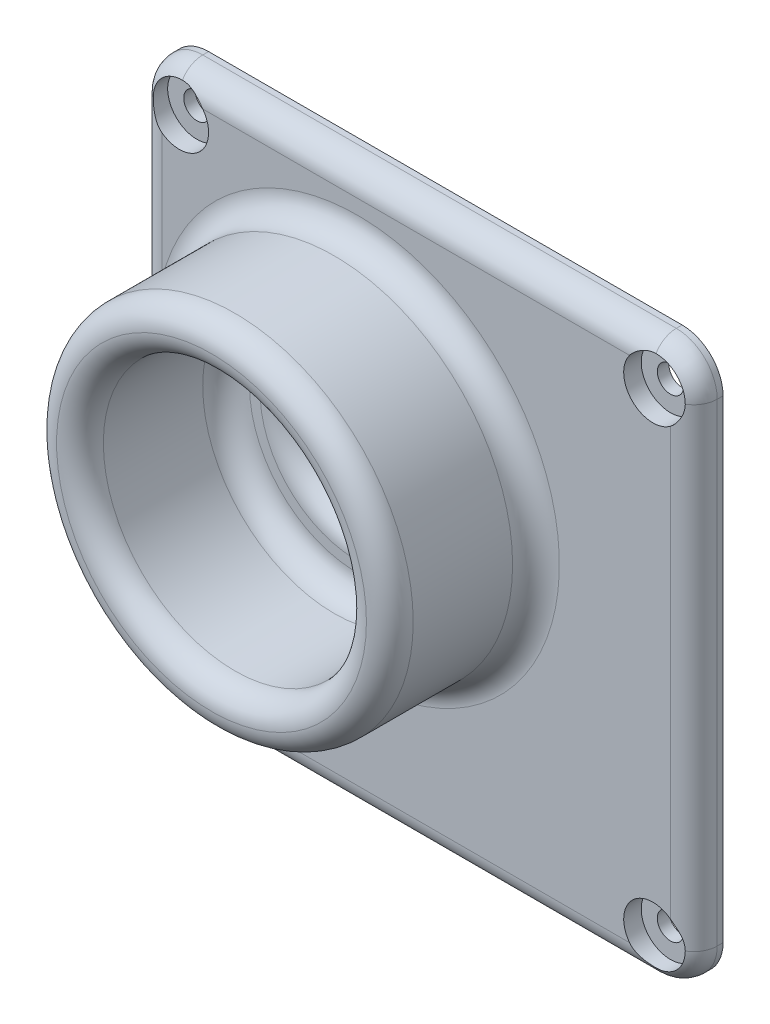
SolidWorks part; units mm, degrees
ref_plane "Front Plane" through (0, 0, 0) normal (1, 0, 0) x (0, 1, 0)
ref_plane "Top Plane" through (0, 0, 0) normal (0, 0, 1) x (0, 1, 0)
ref_plane "Right Plane" through (0, 0, 0) normal (0, 1, 0) x (-1, 0, 0)
sketch "Sketch1" plane through (0, 0, 0) normal (0, 0, 1) x (0, -1, 0)
  line L1 (-37.5, 37.5) -> (37.5, 37.5)
  line L2 (-37.5, 37.5) -> (-37.5, -37.5)
  line L3 (-37.5, -37.5) -> (37.5, -37.5)
  line L4 (37.5, 37.5) -> (37.5, -37.5)
  line L11 (-40.5, 40.5) -> (40.5, 40.5) construction
  line L12 (-40.5, 40.5) -> (-40.5, -40.5) construction
  line L13 (-40.5, -40.5) -> (40.5, -40.5) construction
  line L14 (40.5, 40.5) -> (40.5, -40.5) construction
  line L15 (-40.5, 40.5) -> (40.5, -40.5) construction
  line L16 (-40.5, -40.5) -> (40.5, 40.5) construction
  circle A0 centre (-40.5, 40.5) radius 2.25
  circle A1 centre (40.5, 40.5) radius 2.25
  circle A2 centre (40.5, -40.5) radius 2.25
  circle A3 centre (-40.5, -40.5) radius 2.25
  point P12 (0, 0)
  point P18 (-40.5, 0)
  point P19 (0, 40.5)
  point P20 (0, 37.5)
  point P21 (-37.5, 0)
  dimension "D8" = 4.5
  dimension "D9" = 4.5
  dimension "D3" = 75
  dimension "D4" = 75
  dimension "D7" = 3
sketch "Sketch2" plane through (0, 0, 0) normal (0, 0, 1) x (0, 1, 0)
  line L1 (47.5, -47.5) -> (-47.5, -47.5)
  line L2 (47.5, -47.5) -> (47.5, 47.5)
  line L3 (47.5, 47.5) -> (-47.5, 47.5)
  line L4 (-47.5, -47.5) -> (-47.5, 47.5)
  line L5 (47.5, -47.5) -> (-47.5, 47.5) construction
  line L6 (47.5, 47.5) -> (-47.5, -47.5) construction
  line L7 (37.5, -37.5) -> (-37.5, -37.5) construction
  line L8 (37.5, -37.5) -> (37.5, 37.5) construction
  circle A0 centre (40.5, 40.5) radius 2.25 construction
  circle A1 centre (-40.5, 40.5) radius 2.25 construction
  circle A2 centre (-40.5, -40.5) radius 2.25 construction
  circle A3 centre (40.5, -40.5) radius 2.25 construction
  circle A4 centre (40.5, 40.5) radius 2.25
  circle A5 centre (-40.5, 40.5) radius 2.25
  circle A6 centre (-40.5, -40.5) radius 2.25
  circle A7 centre (40.5, -40.5) radius 2.25
  point P20 (0, 0)
  dimension "D1" = 10
  dimension "D2" = 10
extrude "Boss-Extrude1" add sketch "Sketch2" along normal blind 5
fillet "Fillet1" radius 7 4 edges at (47.5, 47.5, 2.5) (47.5, -47.5, 2.5) (-47.5, -47.5, 2.5) (-47.5, 47.5, 2.5)
fillet "Fillet2" radius 4 8 edges at (0, -47.5, 5) (-47.5, 0, 5) (0, 47.5, 5) (47.5, 0, 5) (45.4497, -45.4497, 5) (-45.4497, -45.4497, 5) (-45.4497, 45.4497, 5) (45.4497, 45.4497, 5)
sketch "Sketch3" plane through (0, 0, 5) normal (0, 0, 1) x (1, 0, 0)
  circle A0 centre (-40.5, -40.5) radius 5
  circle A1 centre (-40.5, 40.5) radius 5
  circle A2 centre (40.5, 40.5) radius 5
  circle A3 centre (40.5, -40.5) radius 5
  dimension "D1" = 10
extrude "Cut-Extrude1" cut sketch "Sketch3" against normal blind 3
sketch "Sketch4" plane through (0, 0, 5) normal (0, 0, 1) x (1, 0, 0)
  circle A0 centre (-10, 6.5) radius 12.7
  circle A1 centre (-40.5, 40.5) radius 2.25 construction
  point P5 (0, 0)
  point P6 (-12.5, 5.5012)
  dimension "D1" = 30.5
  dimension "D2" = 25.4
  dimension "D3" = 11.9269
  dimension "D4" = 6.5
extrude "Cut-Extrude2" cut sketch "Sketch4" against normal through all
fillet "Fillet3" radius 4 1 edges at (2.7, 6.5, 5)
sketch "Sketch5" plane through (0, 0, 5) normal (0, 0, 1) x (1, 0, 0)
  circle A0 centre (-10, 6.5) radius 30.5
  circle A1 centre (-10, 6.5) radius 22.5
  point P4 (0, 0)
  point P5 (-12.1796, 9.1316)
  point P8 (0, 0)
  dimension "D1" = 8
  dimension "D2" = 45
extrude "Boss-Extrude2" add sketch "Sketch5" along normal blind 25
fillet "Fillet4" radius 4 4 edges at (12.5, 6.5, 30) (20.5, 6.5, 30) (12.5, 6.5, 5) (20.5, 6.5, 5)
equation "\"D2@Sketch2\"=\"D1@Sketch2\""
